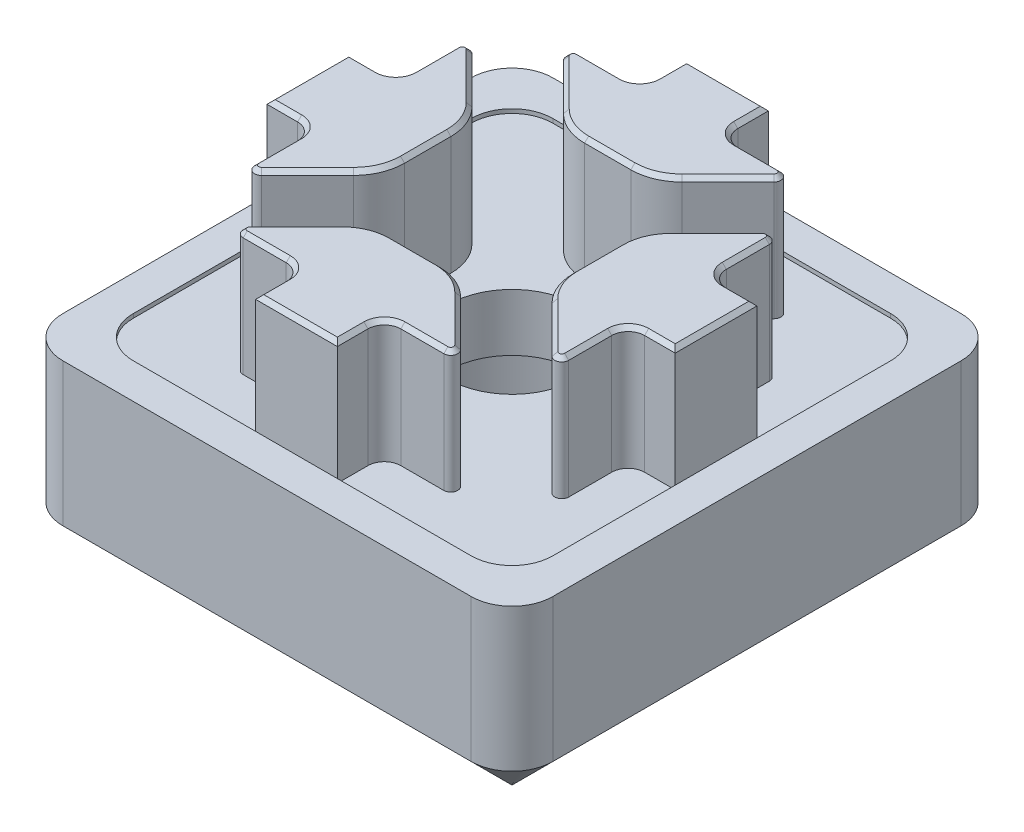
SolidWorks part; units mm, degrees
ref_plane "Front Plane" through (0, 0, 0) normal (0, 0, 1) x (1, 0, 0)
ref_plane "Top Plane" through (0, 0, 0) normal (0, 1, 0) x (1, 0, 0)
ref_plane "Right Plane" through (0, 0, 0) normal (1, 0, 0) x (0, 0, -1)
sketch "Sketch1" plane through (0, 0, 0) normal (0, 1, 0) x (1, 0, 0)
  line L1 (12, 12) -> (-12, 12)
  line L2 (12, 12) -> (12, -12)
  line L3 (12, -12) -> (-12, -12)
  line L4 (-12, 12) -> (-12, -12)
  line L5 (12, 12) -> (-12, -12) construction
  line L6 (12, -12) -> (-12, 12) construction
  circle A0 centre (0, 0) radius 3.15
  point P0 (0, 0)
  dimension "D3" = 6.3
  dimension "D1" = 24
  dimension "D2" = 24
extrude "Boss-Extrude1" add sketch "Sketch1" along normal blind 9
sketch "Sketch2" plane through (0, 9, 0) normal (0, 1, 0) x (1, 0, 0)
  line L1 (10.275, 10.275) -> (-10.275, 10.275)
  line L2 (10.275, 10.275) -> (10.275, -10.275)
  line L3 (10.275, -10.275) -> (-10.275, -10.275)
  line L4 (-10.275, 10.275) -> (-10.275, -10.275)
  line L5 (10.275, 10.275) -> (-10.275, -10.275) construction
  line L6 (10.275, -10.275) -> (-10.275, 10.275) construction
  point P0 (0, 0)
  dimension "D1" = 20.55
extrude "Cut-Extrude1" cut sketch "Sketch2" against normal blind 0.2
sketch "Sketch4" plane through (0, 0, 0) normal (0, -1, 0) x (1, 0, 0)
  circle A0 centre (0, 0) radius 6
extrude "Cut-Extrude2" cut sketch "Sketch4" against normal blind 6
fillet "Fillet1" radius 2 8 edges at (-10.275, 8.9, -10.275) (-10.275, 8.9, 10.275) (10.275, 8.9, 10.275) (10.275, 8.9, -10.275) (12, 4.5, 12) (-12, 4.5, 12) (-12, 4.5, -12) (12, 4.5, -12)
chamfer "Chamfer1" distance 2 angle 45 8 edges at (11.4142, 0, 11.4142) (0, 0, 12) (-11.4142, 0, 11.4142) (-12, 0, 0) (-11.4142, 0, -11.4142) (0, 0, -12) (12, 0, 0) (11.4142, 0, -11.4142)
chamfer "Chamfer2" distance 1 angle 45 1 edges at (0, 0, -6)
sketch "Sketch5" plane through (0, 8.8, 0) normal (0, 1, 0) x (1, 0, 0)
  line L0 (10.275, 9.7148) -> (9.4876, 9.7148)
  line L2 (9.4876, 9.7148) -> (8.7764, 9.7148)
  line L4 (8.7764, 9.7148) -> (8.4716, 9.7148)
  line L6 (8.4716, 9.7148) -> (8.2684, 9.7148)
  line L8 (10.275, 7.7082) -> (10.275, 9.7148)
  line L10 (10.275, 234.725) -> (10.275, 204.7148)
  line L12 (10.275, 204.7148) -> (256.2852, 204.7148)
  line L13 (8.7764, 2.2218) -> (10.275, 2.2218) construction
  line L14 (256.2852, 204.7148) -> (256.2852, 234.725)
  line L16 (256.2852, 234.725) -> (10.275, 234.725)
  line L17 (10.275, -8.275) -> (10.275, 8.275) construction
  line L18 (10.275, 84.7148) -> (256.2852, 84.7148)
  line L20 (256.2852, 84.7148) -> (256.2852, 184.725)
  line L22 (256.2852, 184.725) -> (10.275, 184.725)
  line L24 (10.275, 184.725) -> (10.275, 84.7148)
  line L26 (256.2852, 247.2218) -> (256.2852, 245.8533)
  line L28 (256.2852, 245.8533) -> (256.2852, 243.5865)
  line L30 (256.2852, 243.5865) -> (256.2852, 242.218)
  line L32 (256.2852, 242.218) -> (256.2852, 241.4306)
  line L34 (257.0726, 242.218) -> (257.7838, 242.218)
  line L36 (258.0886, 241.9132) -> (258.0886, 239.805)
  line L38 (259.5195, 239.2123) -> (261.7743, 241.4671)
  line L40 (262.6522, 243.5865) -> (262.6522, 245.8533)
  line L42 (261.7743, 247.9727) -> (259.5195, 250.2275)
  line L44 (258.0886, 249.6348) -> (258.0886, 247.5266)
  line L46 (257.7838, 247.2218) -> (257.0726, 247.2218)
  line L48 (256.2852, 248.0092) -> (256.2852, 247.2218)
  line L50 (256.2852, 234.725) -> (257.0726, 234.725)
  line L52 (257.0726, 234.725) -> (257.7838, 234.725)
  line L54 (257.7838, 234.725) -> (258.0886, 234.725)
  line L56 (258.0886, 234.725) -> (258.2918, 234.725)
  line L58 (256.2852, 236.7316) -> (256.2852, 234.725)
  line L60 (262.9908, 234.725) -> (265.1467, 234.725)
  line L62 (265.1467, 234.725) -> (267.4135, 234.725)
  line L64 (267.4135, 234.725) -> (269.0868, 234.725)
  line L66 (269.0868, 234.725) -> (269.5694, 234.725)
  line L68 (268.782, 235.5124) -> (268.782, 236.2236)
  line L70 (269.0868, 236.5284) -> (271.195, 236.5284)
  line L72 (271.7877, 237.9593) -> (269.5329, 240.2141)
  line L74 (267.4135, 241.092) -> (265.1467, 241.092)
  line L76 (263.0273, 240.2141) -> (260.7725, 237.9593)
  line L78 (261.3652, 236.5284) -> (263.4734, 236.5284)
  line L80 (263.7782, 236.2236) -> (263.7782, 235.5124)
  line L82 (9.4876, 2.2218) -> (8.7764, 2.2218)
  line L84 (8.4716, 2.5266) -> (8.4716, 4.6348)
  line L85 (8.4716, 2.5266) -> (8.4716, 4.6348) construction
  line L86 (7.0407, 5.2275) -> (4.7859, 2.9727)
  line L87 (7.0407, 5.2275) -> (4.7859, 2.9727) construction
  line L88 (3.908, 0.8533) -> (3.908, -1.4135)
  line L89 (3.908, 0.8533) -> (3.908, -1.4135) construction
  line L90 (4.7859, -3.5329) -> (7.0407, -5.7877)
  line L91 (4.7859, -3.5329) -> (7.0407, -5.7877) construction
  line L92 (8.4716, -5.195) -> (8.4716, -3.0868)
  line L93 (8.4716, -5.195) -> (8.4716, -3.0868) construction
  line L94 (8.7764, -2.782) -> (9.4876, -2.782)
  line L96 (10.275, -3.5694) -> (10.275, -3.0868)
  line L98 (10.275, -3.0868) -> (10.275, -2.782)
  line L100 (10.275, -2.782) -> (10.275, -1.4135)
  line L102 (10.275, -1.4135) -> (10.275, 0.8533)
  line L104 (10.275, 0.8533) -> (10.275, 2.5266)
  line L106 (10.275, 2.5266) -> (10.275, 3.0092)
  line L108 (3.0868, 9.7148) -> (2.782, 9.7148)
  line L110 (2.782, 9.7148) -> (1.4135, 9.7148)
  line L112 (1.4135, 9.7148) -> (-0.8533, 9.7148)
  line L114 (-0.8533, 9.7148) -> (-2.5266, 9.7148)
  line L116 (-2.5266, 9.7148) -> (-3.0092, 9.7148)
  line L118 (-2.2218, 8.9274) -> (-2.2218, 8.2162)
  line L120 (-2.5266, 7.9114) -> (-4.6348, 7.9114)
  line L122 (-5.2275, 6.4805) -> (-2.9727, 4.2257)
  line L124 (-0.8533, 3.3478) -> (1.4135, 3.3478)
  line L126 (3.5329, 4.2257) -> (5.7877, 6.4805)
  line L128 (5.195, 7.9114) -> (3.0868, 7.9114)
  line L130 (2.782, 8.2162) -> (2.782, 8.9274)
  line L132 (3.5694, 9.7148) -> (3.0868, 9.7148)
  line L134 (269.0868, 9.7148) -> (268.782, 9.7148)
  line L136 (268.782, 9.7148) -> (267.4135, 9.7148)
  line L138 (267.4135, 9.7148) -> (265.1467, 9.7148)
  line L140 (265.1467, 9.7148) -> (263.4734, 9.7148)
  line L142 (263.4734, 9.7148) -> (262.9908, 9.7148)
  line L144 (263.7782, 8.9274) -> (263.7782, 8.2162)
  line L146 (263.4734, 7.9114) -> (261.3652, 7.9114)
  line L148 (260.7725, 6.4805) -> (263.0273, 4.2257)
  line L150 (265.1467, 3.3478) -> (267.4135, 3.3478)
  line L152 (269.5329, 4.2257) -> (271.7877, 6.4805)
  line L154 (271.195, 7.9114) -> (269.0868, 7.9114)
  line L156 (268.782, 8.2162) -> (268.782, 8.9274)
  line L158 (269.5694, 9.7148) -> (269.0868, 9.7148)
  line L160 (256.2852, 2.5266) -> (256.2852, 2.2218)
  line L162 (256.2852, 2.2218) -> (256.2852, 0.8533)
  line L164 (256.2852, 0.8533) -> (256.2852, -1.4135)
  line L166 (256.2852, -1.4135) -> (256.2852, -3.0868)
  line L168 (256.2852, -3.0868) -> (256.2852, -3.5694)
  line L170 (257.0726, -2.782) -> (257.7838, -2.782)
  line L172 (258.0886, -3.0868) -> (258.0886, -5.195)
  line L174 (259.5195, -5.7877) -> (261.7743, -3.5329)
  line L176 (262.6522, -1.4135) -> (262.6522, 0.8533)
  line L178 (261.7743, 2.9727) -> (259.5195, 5.2275)
  line L180 (258.0886, 4.6348) -> (258.0886, 2.5266)
  line L182 (257.7838, 2.2218) -> (257.0726, 2.2218)
  line L184 (256.2852, 3.0092) -> (256.2852, 2.5266)
  line L186 (-9.7148, 236.7316) -> (-9.7148, 241.4306)
  line L188 (-8.9274, 242.218) -> (-8.2162, 242.218)
  line L190 (-7.9114, 241.9132) -> (-7.9114, 239.805)
  line L192 (-6.4805, 239.2123) -> (-4.2257, 241.4671)
  line L194 (-3.3478, 243.5865) -> (-3.3478, 245.8533)
  line L196 (-4.2257, 247.9727) -> (-6.4805, 250.2275)
  line L198 (-7.9114, 249.6348) -> (-7.9114, 247.5266)
  line L200 (-8.2162, 247.2218) -> (-8.9274, 247.2218)
  line L202 (-9.7148, 248.0092) -> (-9.7148, 252.7082)
  line L204 (-7.7082, 254.7148) -> (-3.0092, 254.7148)
  line L206 (-2.2218, 253.9274) -> (-2.2218, 253.2162)
  line L208 (-2.5266, 252.9114) -> (-4.6348, 252.9114)
  line L210 (-5.2275, 251.4805) -> (-2.9727, 249.2257)
  line L212 (-0.8533, 248.3478) -> (1.4135, 248.3478)
  line L214 (3.5329, 249.2257) -> (5.7877, 251.4805)
  line L216 (5.195, 252.9114) -> (3.0868, 252.9114)
  line L218 (2.782, 253.2162) -> (2.782, 253.9274)
  line L220 (3.5694, 254.7148) -> (8.2684, 254.7148)
  line L222 (10.275, 252.7082) -> (10.275, 252.9114)
  line L224 (10.275, 252.9114) -> (10.275, 253.2162)
  line L226 (10.275, 253.2162) -> (10.275, 253.9274)
  line L228 (10.275, 253.9274) -> (10.275, 254.7148)
  line L230 (10.275, 254.7148) -> (256.2852, 254.7148)
  line L232 (256.2852, 254.7148) -> (256.2852, 252.7082)
  line L234 (258.2918, 254.7148) -> (262.9908, 254.7148)
  line L236 (263.7782, 253.9274) -> (263.7782, 253.2162)
  line L238 (263.4734, 252.9114) -> (261.3652, 252.9114)
  line L240 (260.7725, 251.4805) -> (263.0273, 249.2257)
  line L242 (265.1467, 248.3478) -> (267.4135, 248.3478)
  line L244 (269.5329, 249.2257) -> (271.7877, 251.4805)
  line L246 (271.195, 252.9114) -> (269.0868, 252.9114)
  line L248 (268.782, 253.2162) -> (268.782, 253.9274)
  line L250 (269.5694, 254.7148) -> (274.2684, 254.7148)
  line L252 (276.275, 252.7082) -> (276.275, 248.0092)
  line L254 (275.4876, 247.2218) -> (274.7764, 247.2218)
  line L256 (274.4716, 247.5266) -> (274.4716, 249.6348)
  line L258 (273.0407, 250.2275) -> (270.7859, 247.9727)
  line L260 (269.908, 245.8533) -> (269.908, 243.5865)
  line L262 (270.7859, 241.4671) -> (273.0407, 239.2123)
  line L264 (274.4716, 239.805) -> (274.4716, 241.9132)
  line L266 (274.7764, 242.218) -> (275.4876, 242.218)
  line L268 (276.275, 241.4306) -> (276.275, 236.7316)
  line L270 (274.2684, 234.725) -> (274.4716, 234.725)
  line L272 (274.4716, 234.725) -> (274.7764, 234.725)
  line L274 (274.7764, 234.725) -> (275.4876, 234.725)
  line L276 (275.4876, 234.725) -> (276.275, 234.725)
  line L278 (276.275, 234.725) -> (276.275, 9.7148)
  line L280 (276.275, 9.7148) -> (275.4876, 9.7148)
  line L282 (275.4876, 9.7148) -> (274.7764, 9.7148)
  line L284 (274.7764, 9.7148) -> (274.4716, 9.7148)
  line L286 (274.4716, 9.7148) -> (274.2684, 9.7148)
  line L288 (276.275, 7.7082) -> (276.275, 3.0092)
  line L290 (275.4876, 2.2218) -> (274.7764, 2.2218)
  line L292 (274.4716, 2.5266) -> (274.4716, 4.6348)
  line L294 (273.0407, 5.2275) -> (270.7859, 2.9727)
  line L296 (269.908, 0.8533) -> (269.908, -1.4135)
  line L298 (270.7859, -3.5329) -> (273.0407, -5.7877)
  line L300 (274.4716, -5.195) -> (274.4716, -3.0868)
  line L302 (274.7764, -2.782) -> (275.4876, -2.782)
  line L304 (276.275, -3.5694) -> (276.275, -8.2684)
  line L306 (274.2684, -10.275) -> (269.5694, -10.275)
  line L308 (268.782, -9.4876) -> (268.782, -8.7764)
  line L310 (269.0868, -8.4716) -> (271.195, -8.4716)
  line L312 (271.7877, -7.0407) -> (269.5329, -4.7859)
  line L314 (267.4135, -3.908) -> (265.1467, -3.908)
  line L316 (263.0273, -4.7859) -> (260.7725, -7.0407)
  line L318 (261.3652, -8.4716) -> (263.4734, -8.4716)
  line L320 (263.7782, -8.7764) -> (263.7782, -9.4876)
  line L322 (262.9908, -10.275) -> (258.2918, -10.275)
  line L324 (256.2852, -8.2684) -> (256.2852, -8.4716)
  line L326 (256.2852, -8.4716) -> (256.2852, -8.7764)
  line L328 (256.2852, -8.7764) -> (256.2852, -9.4876)
  line L330 (256.2852, -9.4876) -> (256.2852, -10.275)
  line L332 (256.2852, -10.275) -> (10.275, -10.275)
  line L334 (10.275, -10.275) -> (10.275, -9.4876)
  line L336 (10.275, -9.4876) -> (10.275, -8.7764)
  line L338 (10.275, -8.7764) -> (10.275, -8.4716)
  line L340 (10.275, -8.4716) -> (10.275, -8.2684)
  line L341 (10.275, -8.4716) -> (10.275, -8.2684)
  line L342 (8.2684, -10.275) -> (3.5694, -10.275)
  line L344 (2.782, -9.4876) -> (2.782, -8.7764)
  line L346 (3.0868, -8.4716) -> (5.195, -8.4716)
  line L348 (5.7877, -7.0407) -> (3.5329, -4.7859)
  line L350 (1.4135, -3.908) -> (-0.8533, -3.908)
  line L352 (-2.9727, -4.7859) -> (-5.2275, -7.0407)
  line L354 (-4.6348, -8.4716) -> (-2.5266, -8.4716)
  line L356 (-2.2218, -8.7764) -> (-2.2218, -9.4876)
  line L358 (-3.0092, -10.275) -> (-7.7082, -10.275)
  line L360 (-9.7148, -8.2684) -> (-9.7148, -3.5694)
  line L362 (-8.9274, -2.782) -> (-8.2162, -2.782)
  line L364 (-7.9114, -3.0868) -> (-7.9114, -5.195)
  line L366 (-6.4805, -5.7877) -> (-4.2257, -3.5329)
  line L368 (-3.3478, -1.4135) -> (-3.3478, 0.8533)
  line L370 (-4.2257, 2.9727) -> (-6.4805, 5.2275)
  line L372 (-7.9114, 4.6348) -> (-7.9114, 2.5266)
  line L374 (-8.2162, 2.2218) -> (-8.9274, 2.2218)
  line L376 (-9.7148, 3.0092) -> (-9.7148, 7.7082)
  line L378 (-7.7082, 9.7148) -> (-7.9114, 9.7148)
  line L380 (-7.9114, 9.7148) -> (-8.2162, 9.7148)
  line L382 (-8.2162, 9.7148) -> (-8.9274, 9.7148)
  line L384 (-8.9274, 9.7148) -> (-9.7148, 9.7148)
  line L386 (-9.7148, 9.7148) -> (-9.7148, 234.725)
  line L388 (-9.7148, 234.725) -> (-8.9274, 234.725)
  line L390 (-8.9274, 234.725) -> (-8.2162, 234.725)
  line L392 (-8.2162, 234.725) -> (-7.9114, 234.725)
  line L394 (-7.9114, 234.725) -> (-7.7082, 234.725)
  line L396 (-2.5266, 234.725) -> (-2.2218, 234.725)
  line L398 (-2.2218, 234.725) -> (-0.8533, 234.725)
  line L400 (-0.8533, 234.725) -> (1.4135, 234.725)
  line L402 (1.4135, 234.725) -> (3.0868, 234.725)
  line L404 (3.0868, 234.725) -> (3.5694, 234.725)
  line L406 (2.782, 235.5124) -> (2.782, 236.2236)
  line L408 (3.0868, 236.5284) -> (5.195, 236.5284)
  line L410 (5.7877, 237.9593) -> (3.5329, 240.2141)
  line L412 (1.4135, 241.092) -> (-0.8533, 241.092)
  line L414 (-2.9727, 240.2141) -> (-5.2275, 237.9593)
  line L416 (-4.6348, 236.5284) -> (-2.5266, 236.5284)
  line L418 (-2.2218, 236.2236) -> (-2.2218, 235.5124)
  line L420 (-3.0092, 234.725) -> (-2.5266, 234.725)
  line L422 (8.4716, 234.725) -> (8.7764, 234.725)
  line L424 (8.7764, 234.725) -> (9.4876, 234.725)
  line L426 (9.4876, 234.725) -> (10.275, 234.725)
  line L428 (10.275, 234.725) -> (10.275, 236.7316)
  line L430 (8.2684, 234.725) -> (8.4716, 234.725)
  line L432 (9.4876, 247.2218) -> (8.7764, 247.2218)
  line L434 (8.4716, 247.5266) -> (8.4716, 249.6348)
  line L436 (7.0407, 250.2275) -> (4.7859, 247.9727)
  line L438 (3.908, 245.8533) -> (3.908, 243.5865)
  line L440 (4.7859, 241.4671) -> (7.0407, 239.2123)
  line L442 (8.4716, 239.805) -> (8.4716, 241.9132)
  line L444 (8.7764, 242.218) -> (9.4876, 242.218)
  line L446 (10.275, 241.4306) -> (10.275, 242.218)
  line L448 (10.275, 242.218) -> (10.275, 243.5865)
  line L450 (10.275, 243.5865) -> (10.275, 245.8533)
  line L452 (10.275, 245.8533) -> (10.275, 248.0092)
  line L454 (256.2852, 8.9274) -> (256.2852, 8.2162)
  line L456 (256.2852, 8.2162) -> (256.2852, 7.9114)
  line L458 (256.2852, 7.9114) -> (256.2852, 7.7082)
  line L460 (258.2918, 9.7148) -> (256.2852, 9.7148)
  line L462 (256.2852, 9.7148) -> (256.2852, 8.9274)
  line L464 (256.2852, 9.7148) -> (256.2852, 64.725)
  line L466 (256.2852, 64.725) -> (10.275, 64.725)
  line L467 (8.7764, -2.782) -> (10.275, -2.782) construction
  line L468 (10.275, 64.725) -> (10.275, 9.7148)
  line L470 (10.275, 9.7148) -> (256.2852, 9.7148)
  line L471 (10.275, 2.2218) -> (10.275, -2.782) construction
  line L475 (7.9716, -5.195) -> (7.9716, -3.0868)
  line L476 (5.1394, -3.1793) -> (7.3943, -5.4341)
  line L477 (4.408, 0.8533) -> (4.408, -1.4135)
  line L478 (7.3943, 4.8739) -> (5.1394, 2.6191)
  line L479 (7.9716, 2.5266) -> (7.9716, 4.6348)
  line L480 (8.7764, -2.282) -> (10.275, -2.282)
  line L481 (8.7764, 1.7218) -> (10.275, 1.7218)
  line L482 (10.275, 1.7218) -> (10.275, -2.282)
  line L483 (1.7218, -10.275) -> (-2.282, -10.275)
  line L484 (-2.282, -8.7764) -> (-2.282, -10.275)
  line L485 (-5.195, -7.9716) -> (-3.0868, -7.9716)
  line L486 (-3.1793, -5.1394) -> (-5.4341, -7.3943)
  line L487 (0.8533, -4.408) -> (-1.4135, -4.408)
  line L488 (4.8739, -7.3943) -> (2.6191, -5.1394)
  line L489 (2.5266, -7.9716) -> (4.6348, -7.9716)
  line L490 (1.7218, -8.7764) -> (1.7218, -10.275)
  line L491 (-10.275, -1.7218) -> (-10.275, 2.282)
  line L492 (-8.7764, 2.282) -> (-10.275, 2.282)
  line L493 (-7.9716, 5.195) -> (-7.9716, 3.0868)
  line L494 (-5.1394, 3.1793) -> (-7.3943, 5.4341)
  line L495 (-4.408, -0.8533) -> (-4.408, 1.4135)
  line L496 (-7.3943, -4.8739) -> (-5.1394, -2.6191)
  line L497 (-7.9716, -2.5266) -> (-7.9716, -4.6348)
  line L498 (-8.7764, -1.7218) -> (-10.275, -1.7218)
  line L499 (-1.7218, 10.275) -> (2.282, 10.275)
  line L500 (2.282, 8.7764) -> (2.282, 10.275)
  line L501 (5.195, 7.9716) -> (3.0868, 7.9716)
  line L502 (3.1793, 5.1394) -> (5.4341, 7.3943)
  line L503 (-0.8533, 4.408) -> (1.4135, 4.408)
  line L504 (-4.8739, 7.3943) -> (-2.6191, 5.1394)
  line L505 (-2.5266, 7.9716) -> (-4.6348, 7.9716)
  line L506 (-1.7218, 8.7764) -> (-1.7218, 10.275)
  line L716 (9.775, 1.7218) -> (9.775, -2.282) construction
  line L717 (8.7764, -2.282) -> (9.775, -2.282) construction
  line L718 (8.7764, 1.7218) -> (9.775, 1.7218) construction
  arc A0 (10.275, 7.7082) -> (8.2684, 9.7148) centre (8.2684, 7.7082) ccw
  circle A2 centre (266.2801, 244.7199) radius 2.1463
  arc A4 (257.0726, 242.218) -> (256.2852, 241.4306) centre (257.0726, 241.4306) ccw
  arc A6 (258.0886, 241.9132) -> (257.7838, 242.218) centre (257.7838, 241.9132) ccw
  arc A8 (258.0886, 239.805) -> (259.5195, 239.2123) centre (258.9268, 239.805) ccw
  arc A10 (261.7743, 241.4671) -> (262.6522, 243.5865) centre (259.655, 243.5865) ccw
  arc A12 (262.6522, 245.8533) -> (261.7743, 247.9727) centre (259.655, 245.8533) ccw
  arc A14 (259.5195, 250.2275) -> (258.0886, 249.6348) centre (258.9268, 249.6348) ccw
  arc A16 (257.7838, 247.2218) -> (258.0886, 247.5266) centre (257.7838, 247.5266) ccw
  arc A18 (256.2852, 248.0092) -> (257.0726, 247.2218) centre (257.0726, 248.0092) ccw
  arc A20 (256.2852, 236.7316) -> (258.2918, 234.725) centre (258.2918, 236.7316) ccw
  arc A22 (268.782, 235.5124) -> (269.5694, 234.725) centre (269.5694, 235.5124) ccw
  arc A24 (269.0868, 236.5284) -> (268.782, 236.2236) centre (269.0868, 236.2236) ccw
  arc A26 (271.195, 236.5284) -> (271.7877, 237.9593) centre (271.195, 237.3666) ccw
  arc A28 (269.5329, 240.2141) -> (267.4135, 241.092) centre (267.4135, 238.0948) ccw
  arc A30 (265.1467, 241.092) -> (263.0273, 240.2141) centre (265.1467, 238.0948) ccw
  arc A32 (260.7725, 237.9593) -> (261.3652, 236.5284) centre (261.3652, 237.3666) ccw
  arc A34 (263.7782, 236.2236) -> (263.4734, 236.5284) centre (263.4734, 236.2236) ccw
  arc A36 (262.9908, 234.725) -> (263.7782, 235.5124) centre (262.9908, 235.5124) ccw
  circle A38 centre (0.2801, -0.2801) radius 2.1463
  arc A40 (8.4716, 2.5266) -> (8.7764, 2.2218) centre (8.7764, 2.5266) ccw
  arc A41 (8.4716, 2.5266) -> (8.7764, 2.2218) centre (8.7764, 2.5266) ccw construction
  arc A42 (8.4716, 4.6348) -> (7.0407, 5.2275) centre (7.6334, 4.6348) ccw
  arc A43 (8.4716, 4.6348) -> (7.0407, 5.2275) centre (7.6334, 4.6348) ccw construction
  arc A44 (4.7859, 2.9727) -> (3.908, 0.8533) centre (6.9052, 0.8533) ccw
  arc A45 (4.7859, 2.9727) -> (3.908, 0.8533) centre (6.9052, 0.8533) ccw construction
  arc A46 (3.908, -1.4135) -> (4.7859, -3.5329) centre (6.9052, -1.4135) ccw
  arc A47 (3.908, -1.4135) -> (4.7859, -3.5329) centre (6.9052, -1.4135) ccw construction
  arc A48 (7.0407, -5.7877) -> (8.4716, -5.195) centre (7.6334, -5.195) ccw
  arc A49 (7.0407, -5.7877) -> (8.4716, -5.195) centre (7.6334, -5.195) ccw construction
  arc A50 (8.7764, -2.782) -> (8.4716, -3.0868) centre (8.7764, -3.0868) ccw
  arc A51 (8.7764, -2.782) -> (8.4716, -3.0868) centre (8.7764, -3.0868) ccw construction
  arc A52 (10.275, -3.5694) -> (9.4876, -2.782) centre (9.4876, -3.5694) ccw
  arc A54 (9.4876, 2.2218) -> (10.275, 3.0092) centre (9.4876, 3.0092) ccw
  arc A56 (-2.2218, 8.9274) -> (-3.0092, 9.7148) centre (-3.0092, 8.9274) ccw
  arc A58 (-2.5266, 7.9114) -> (-2.2218, 8.2162) centre (-2.5266, 8.2162) ccw
  arc A60 (-4.6348, 7.9114) -> (-5.2275, 6.4805) centre (-4.6348, 7.0732) ccw
  arc A62 (-2.9727, 4.2257) -> (-0.8533, 3.3478) centre (-0.8533, 6.345) ccw
  arc A64 (1.4135, 3.3478) -> (3.5329, 4.2257) centre (1.4135, 6.345) ccw
  arc A66 (5.7877, 6.4805) -> (5.195, 7.9114) centre (5.195, 7.0732) ccw
  arc A68 (2.782, 8.2162) -> (3.0868, 7.9114) centre (3.0868, 8.2162) ccw
  arc A70 (3.5694, 9.7148) -> (2.782, 8.9274) centre (3.5694, 8.9274) ccw
  circle A72 centre (266.2801, -0.2801) radius 2.1463
  arc A74 (263.7782, 8.9274) -> (262.9908, 9.7148) centre (262.9908, 8.9274) ccw
  arc A76 (263.4734, 7.9114) -> (263.7782, 8.2162) centre (263.4734, 8.2162) ccw
  arc A78 (261.3652, 7.9114) -> (260.7725, 6.4805) centre (261.3652, 7.0732) ccw
  arc A80 (263.0273, 4.2257) -> (265.1467, 3.3478) centre (265.1467, 6.345) ccw
  arc A82 (267.4135, 3.3478) -> (269.5329, 4.2257) centre (267.4135, 6.345) ccw
  arc A84 (271.7877, 6.4805) -> (271.195, 7.9114) centre (271.195, 7.0732) ccw
  arc A86 (268.782, 8.2162) -> (269.0868, 7.9114) centre (269.0868, 8.2162) ccw
  arc A88 (269.5694, 9.7148) -> (268.782, 8.9274) centre (269.5694, 8.9274) ccw
  arc A90 (257.0726, -2.782) -> (256.2852, -3.5694) centre (257.0726, -3.5694) ccw
  arc A92 (258.0886, -3.0868) -> (257.7838, -2.782) centre (257.7838, -3.0868) ccw
  arc A94 (258.0886, -5.195) -> (259.5195, -5.7877) centre (258.9268, -5.195) ccw
  arc A96 (261.7743, -3.5329) -> (262.6522, -1.4135) centre (259.655, -1.4135) ccw
  arc A98 (262.6522, 0.8533) -> (261.7743, 2.9727) centre (259.655, 0.8533) ccw
  arc A100 (259.5195, 5.2275) -> (258.0886, 4.6348) centre (258.9268, 4.6348) ccw
  arc A102 (257.7838, 2.2218) -> (258.0886, 2.5266) centre (257.7838, 2.5266) ccw
  arc A104 (256.2852, 3.0092) -> (257.0726, 2.2218) centre (257.0726, 3.0092) ccw
  circle A106 centre (0.2801, 244.7199) radius 2.1463
  arc A108 (-8.9274, 242.218) -> (-9.7148, 241.4306) centre (-8.9274, 241.4306) ccw
  arc A110 (-7.9114, 241.9132) -> (-8.2162, 242.218) centre (-8.2162, 241.9132) ccw
  arc A112 (-7.9114, 239.805) -> (-6.4805, 239.2123) centre (-7.0732, 239.805) ccw
  arc A114 (-4.2257, 241.4671) -> (-3.3478, 243.5865) centre (-6.345, 243.5865) ccw
  arc A116 (-3.3478, 245.8533) -> (-4.2257, 247.9727) centre (-6.345, 245.8533) ccw
  arc A118 (-6.4805, 250.2275) -> (-7.9114, 249.6348) centre (-7.0732, 249.6348) ccw
  arc A120 (-8.2162, 247.2218) -> (-7.9114, 247.5266) centre (-8.2162, 247.5266) ccw
  arc A122 (-9.7148, 248.0092) -> (-8.9274, 247.2218) centre (-8.9274, 248.0092) ccw
  arc A124 (-7.7082, 254.7148) -> (-9.7148, 252.7082) centre (-7.7082, 252.7082) ccw
  arc A126 (-2.2218, 253.9274) -> (-3.0092, 254.7148) centre (-3.0092, 253.9274) ccw
  arc A128 (-2.5266, 252.9114) -> (-2.2218, 253.2162) centre (-2.5266, 253.2162) ccw
  arc A130 (-4.6348, 252.9114) -> (-5.2275, 251.4805) centre (-4.6348, 252.0732) ccw
  arc A132 (-2.9727, 249.2257) -> (-0.8533, 248.3478) centre (-0.8533, 251.345) ccw
  arc A134 (1.4135, 248.3478) -> (3.5329, 249.2257) centre (1.4135, 251.345) ccw
  arc A136 (5.7877, 251.4805) -> (5.195, 252.9114) centre (5.195, 252.0732) ccw
  arc A138 (2.782, 253.2162) -> (3.0868, 252.9114) centre (3.0868, 253.2162) ccw
  arc A140 (3.5694, 254.7148) -> (2.782, 253.9274) centre (3.5694, 253.9274) ccw
  arc A142 (10.275, 252.7082) -> (8.2684, 254.7148) centre (8.2684, 252.7082) ccw
  arc A144 (258.2918, 254.7148) -> (256.2852, 252.7082) centre (258.2918, 252.7082) ccw
  arc A146 (263.7782, 253.9274) -> (262.9908, 254.7148) centre (262.9908, 253.9274) ccw
  arc A148 (263.4734, 252.9114) -> (263.7782, 253.2162) centre (263.4734, 253.2162) ccw
  arc A150 (261.3652, 252.9114) -> (260.7725, 251.4805) centre (261.3652, 252.0732) ccw
  arc A152 (263.0273, 249.2257) -> (265.1467, 248.3478) centre (265.1467, 251.345) ccw
  arc A154 (267.4135, 248.3478) -> (269.5329, 249.2257) centre (267.4135, 251.345) ccw
  arc A156 (271.7877, 251.4805) -> (271.195, 252.9114) centre (271.195, 252.0732) ccw
  arc A158 (268.782, 253.2162) -> (269.0868, 252.9114) centre (269.0868, 253.2162) ccw
  arc A160 (269.5694, 254.7148) -> (268.782, 253.9274) centre (269.5694, 253.9274) ccw
  arc A162 (276.275, 252.7082) -> (274.2684, 254.7148) centre (274.2684, 252.7082) ccw
  arc A164 (275.4876, 247.2218) -> (276.275, 248.0092) centre (275.4876, 248.0092) ccw
  arc A166 (274.4716, 247.5266) -> (274.7764, 247.2218) centre (274.7764, 247.5266) ccw
  arc A168 (274.4716, 249.6348) -> (273.0407, 250.2275) centre (273.6334, 249.6348) ccw
  arc A170 (270.7859, 247.9727) -> (269.908, 245.8533) centre (272.9052, 245.8533) ccw
  arc A172 (269.908, 243.5865) -> (270.7859, 241.4671) centre (272.9052, 243.5865) ccw
  arc A174 (273.0407, 239.2123) -> (274.4716, 239.805) centre (273.6334, 239.805) ccw
  arc A176 (274.7764, 242.218) -> (274.4716, 241.9132) centre (274.7764, 241.9132) ccw
  arc A178 (276.275, 241.4306) -> (275.4876, 242.218) centre (275.4876, 241.4306) ccw
  arc A180 (274.2684, 234.725) -> (276.275, 236.7316) centre (274.2684, 236.7316) ccw
  arc A182 (276.275, 7.7082) -> (274.2684, 9.7148) centre (274.2684, 7.7082) ccw
  arc A184 (275.4876, 2.2218) -> (276.275, 3.0092) centre (275.4876, 3.0092) ccw
  arc A186 (274.4716, 2.5266) -> (274.7764, 2.2218) centre (274.7764, 2.5266) ccw
  arc A188 (274.4716, 4.6348) -> (273.0407, 5.2275) centre (273.6334, 4.6348) ccw
  arc A190 (270.7859, 2.9727) -> (269.908, 0.8533) centre (272.9052, 0.8533) ccw
  arc A192 (269.908, -1.4135) -> (270.7859, -3.5329) centre (272.9052, -1.4135) ccw
  arc A194 (273.0407, -5.7877) -> (274.4716, -5.195) centre (273.6334, -5.195) ccw
  arc A196 (274.7764, -2.782) -> (274.4716, -3.0868) centre (274.7764, -3.0868) ccw
  arc A198 (276.275, -3.5694) -> (275.4876, -2.782) centre (275.4876, -3.5694) ccw
  arc A200 (274.2684, -10.275) -> (276.275, -8.2684) centre (274.2684, -8.2684) ccw
  arc A202 (268.782, -9.4876) -> (269.5694, -10.275) centre (269.5694, -9.4876) ccw
  arc A204 (269.0868, -8.4716) -> (268.782, -8.7764) centre (269.0868, -8.7764) ccw
  arc A206 (271.195, -8.4716) -> (271.7877, -7.0407) centre (271.195, -7.6334) ccw
  arc A208 (269.5329, -4.7859) -> (267.4135, -3.908) centre (267.4135, -6.9052) ccw
  arc A210 (265.1467, -3.908) -> (263.0273, -4.7859) centre (265.1467, -6.9052) ccw
  arc A212 (260.7725, -7.0407) -> (261.3652, -8.4716) centre (261.3652, -7.6334) ccw
  arc A214 (263.7782, -8.7764) -> (263.4734, -8.4716) centre (263.4734, -8.7764) ccw
  arc A216 (262.9908, -10.275) -> (263.7782, -9.4876) centre (262.9908, -9.4876) ccw
  arc A218 (256.2852, -8.2684) -> (258.2918, -10.275) centre (258.2918, -8.2684) ccw
  arc A220 (8.2684, -10.275) -> (10.275, -8.2684) centre (8.2684, -8.2684) ccw
  arc A222 (2.782, -9.4876) -> (3.5694, -10.275) centre (3.5694, -9.4876) ccw
  arc A224 (3.0868, -8.4716) -> (2.782, -8.7764) centre (3.0868, -8.7764) ccw
  arc A226 (5.195, -8.4716) -> (5.7877, -7.0407) centre (5.195, -7.6334) ccw
  arc A228 (3.5329, -4.7859) -> (1.4135, -3.908) centre (1.4135, -6.9052) ccw
  arc A230 (-0.8533, -3.908) -> (-2.9727, -4.7859) centre (-0.8533, -6.9052) ccw
  arc A232 (-5.2275, -7.0407) -> (-4.6348, -8.4716) centre (-4.6348, -7.6334) ccw
  arc A234 (-2.2218, -8.7764) -> (-2.5266, -8.4716) centre (-2.5266, -8.7764) ccw
  arc A236 (-3.0092, -10.275) -> (-2.2218, -9.4876) centre (-3.0092, -9.4876) ccw
  arc A238 (-9.7148, -8.2684) -> (-7.7082, -10.275) centre (-7.7082, -8.2684) ccw
  arc A240 (-8.9274, -2.782) -> (-9.7148, -3.5694) centre (-8.9274, -3.5694) ccw
  arc A242 (-7.9114, -3.0868) -> (-8.2162, -2.782) centre (-8.2162, -3.0868) ccw
  arc A244 (-7.9114, -5.195) -> (-6.4805, -5.7877) centre (-7.0732, -5.195) ccw
  arc A246 (-4.2257, -3.5329) -> (-3.3478, -1.4135) centre (-6.345, -1.4135) ccw
  arc A248 (-3.3478, 0.8533) -> (-4.2257, 2.9727) centre (-6.345, 0.8533) ccw
  arc A250 (-6.4805, 5.2275) -> (-7.9114, 4.6348) centre (-7.0732, 4.6348) ccw
  arc A252 (-8.2162, 2.2218) -> (-7.9114, 2.5266) centre (-8.2162, 2.5266) ccw
  arc A254 (-9.7148, 3.0092) -> (-8.9274, 2.2218) centre (-8.9274, 3.0092) ccw
  arc A256 (-7.7082, 9.7148) -> (-9.7148, 7.7082) centre (-7.7082, 7.7082) ccw
  arc A258 (-9.7148, 236.7316) -> (-7.7082, 234.725) centre (-7.7082, 236.7316) ccw
  arc A260 (2.782, 235.5124) -> (3.5694, 234.725) centre (3.5694, 235.5124) ccw
  arc A262 (3.0868, 236.5284) -> (2.782, 236.2236) centre (3.0868, 236.2236) ccw
  arc A264 (5.195, 236.5284) -> (5.7877, 237.9593) centre (5.195, 237.3666) ccw
  arc A266 (3.5329, 240.2141) -> (1.4135, 241.092) centre (1.4135, 238.0948) ccw
  arc A268 (-0.8533, 241.092) -> (-2.9727, 240.2141) centre (-0.8533, 238.0948) ccw
  arc A270 (-5.2275, 237.9593) -> (-4.6348, 236.5284) centre (-4.6348, 237.3666) ccw
  arc A272 (-2.2218, 236.2236) -> (-2.5266, 236.5284) centre (-2.5266, 236.2236) ccw
  arc A274 (-3.0092, 234.725) -> (-2.2218, 235.5124) centre (-3.0092, 235.5124) ccw
  arc A276 (8.2684, 234.725) -> (10.275, 236.7316) centre (8.2684, 236.7316) ccw
  arc A278 (9.4876, 247.2218) -> (10.275, 248.0092) centre (9.4876, 248.0092) ccw
  arc A280 (8.4716, 247.5266) -> (8.7764, 247.2218) centre (8.7764, 247.5266) ccw
  arc A282 (8.4716, 249.6348) -> (7.0407, 250.2275) centre (7.6334, 249.6348) ccw
  arc A284 (4.7859, 247.9727) -> (3.908, 245.8533) centre (6.9052, 245.8533) ccw
  arc A286 (3.908, 243.5865) -> (4.7859, 241.4671) centre (6.9052, 243.5865) ccw
  arc A288 (7.0407, 239.2123) -> (8.4716, 239.805) centre (7.6334, 239.805) ccw
  arc A290 (8.7764, 242.218) -> (8.4716, 241.9132) centre (8.7764, 241.9132) ccw
  arc A292 (10.275, 241.4306) -> (9.4876, 242.218) centre (9.4876, 241.4306) ccw
  arc A294 (258.2918, 9.7148) -> (256.2852, 7.7082) centre (258.2918, 7.7082) ccw
  arc A296 (8.7764, -2.282) -> (7.9716, -3.0868) centre (8.7764, -3.0868) ccw
  arc A297 (7.3943, -5.4341) -> (7.9716, -5.195) centre (7.6334, -5.195) ccw
  arc A298 (4.408, -1.4135) -> (5.1394, -3.1793) centre (6.9052, -1.4135) ccw
  arc A299 (5.1394, 2.6191) -> (4.408, 0.8533) centre (6.9052, 0.8533) ccw
  arc A300 (7.9716, 4.6348) -> (7.3943, 4.8739) centre (7.6334, 4.6348) ccw
  arc A301 (7.9716, 2.5266) -> (8.7764, 1.7218) centre (8.7764, 2.5266) ccw
  arc A302 (-2.282, -8.7764) -> (-3.0868, -7.9716) centre (-3.0868, -8.7764) ccw
  arc A303 (-5.4341, -7.3943) -> (-5.195, -7.9716) centre (-5.195, -7.6334) ccw
  arc A304 (-1.4135, -4.408) -> (-3.1793, -5.1394) centre (-1.4135, -6.9052) ccw
  arc A305 (2.6191, -5.1394) -> (0.8533, -4.408) centre (0.8533, -6.9052) ccw
  arc A306 (4.6348, -7.9716) -> (4.8739, -7.3943) centre (4.6348, -7.6334) ccw
  arc A307 (2.5266, -7.9716) -> (1.7218, -8.7764) centre (2.5266, -8.7764) ccw
  arc A308 (-8.7764, 2.282) -> (-7.9716, 3.0868) centre (-8.7764, 3.0868) ccw
  arc A309 (-7.3943, 5.4341) -> (-7.9716, 5.195) centre (-7.6334, 5.195) ccw
  arc A310 (-4.408, 1.4135) -> (-5.1394, 3.1793) centre (-6.9052, 1.4135) ccw
  arc A311 (-5.1394, -2.6191) -> (-4.408, -0.8533) centre (-6.9052, -0.8533) ccw
  arc A312 (-7.9716, -4.6348) -> (-7.3943, -4.8739) centre (-7.6334, -4.6348) ccw
  arc A313 (-7.9716, -2.5266) -> (-8.7764, -1.7218) centre (-8.7764, -2.5266) ccw
  arc A314 (2.282, 8.7764) -> (3.0868, 7.9716) centre (3.0868, 8.7764) ccw
  arc A315 (5.4341, 7.3943) -> (5.195, 7.9716) centre (5.195, 7.6334) ccw
  arc A316 (1.4135, 4.408) -> (3.1793, 5.1394) centre (1.4135, 6.9052) ccw
  arc A317 (-2.6191, 5.1394) -> (-0.8533, 4.408) centre (-0.8533, 6.9052) ccw
  arc A318 (-4.6348, 7.9716) -> (-4.8739, 7.3943) centre (-4.6348, 7.6334) ccw
  arc A319 (-2.5266, 7.9716) -> (-1.7218, 8.7764) centre (-2.5266, 8.7764) ccw
  point P617 (0, 0)
  line M212 (8.275, 10.275) -> (-8.275, 10.275)
  line M214 (-10.275, 8.275) -> (-10.275, -8.275)
  line M216 (-8.275, -10.275) -> (8.275, -10.275)
  line M218 (10.275, -8.275) -> (10.275, 8.275)
  dimension "D1" = 0.5
  dimension "D2" = 4
extrude "Boss-Extrude2" add sketch "Sketch5" along normal blind 6 contours A319 L505 A318 L504 A317 L503 A316 L502 A315 L501 A314 L500 L506 M212 | A313 L497 A312 L496 A311 L495 A310 L494 A309 L493 A308 L492 L498 M214 | A307 L489 A306 L488 A305 L487 A304 L486 A303 L485 A302 L484 L490 M216 | A301 L479 A300 L478 A299 L477 A298 L476 A297 L475 A296 L480 L481 M218
chamfer "Chamfer3" distance 0.2 angle 45 56 edges at (-1.7218, 14.8, -9.5257) (0.2801, 14.8, -10.275) (2.282, 14.8, -9.5257) (2.5177, 14.8, -8.2073) (4.1409, 14.8, -7.9716) (5.5075, 14.8, -7.7628) (4.3067, 14.8, -6.2668) (2.3692, 14.8, -4.5981) (0.2801, 14.8, -4.408) (-1.809, 14.8, -4.5981) (-3.7465, 14.8, -6.2668) (-4.9473, 14.8, -7.7628) (-3.5807, 14.8, -7.9716) (-1.9575, 14.8, -8.2073) (-9.5257, 14.8, 1.7218) (-10.275, 14.8, -0.2801) (-9.5257, 14.8, -2.282) (-8.2073, 14.8, -2.5177) (-7.9716, 14.8, -4.1409) (-7.7628, 14.8, -5.5075) (-6.2668, 14.8, -4.3067) (-4.5981, 14.8, -2.3692) (-4.408, 14.8, -0.2801) (-4.5981, 14.8, 1.809) (-6.2668, 14.8, 3.7465) (-7.7628, 14.8, 4.9473) (-7.9716, 14.8, 3.5807) (-8.2073, 14.8, 1.9575) (1.7218, 14.8, 9.5257) (-0.2801, 14.8, 10.275) (-2.282, 14.8, 9.5257) (-2.5177, 14.8, 8.2073) (-4.1409, 14.8, 7.9716) (-5.5075, 14.8, 7.7628) (-4.3067, 14.8, 6.2668) (-2.3692, 14.8, 4.5981) (-0.2801, 14.8, 4.408) (1.809, 14.8, 4.5981) (3.7465, 14.8, 6.2668) (4.9473, 14.8, 7.7628) (3.5807, 14.8, 7.9716) (1.9575, 14.8, 8.2073) (9.5257, 14.8, -1.7218) (10.275, 14.8, 0.2801) (9.5257, 14.8, 2.282) (8.2073, 14.8, 2.5177) (7.9716, 14.8, 4.1409) (7.7628, 14.8, 5.5075) (6.2668, 14.8, 4.3067) (4.5981, 14.8, 2.3692) (4.408, 14.8, 0.2801) (4.5981, 14.8, -1.809) (6.2668, 14.8, -3.7465) (7.7628, 14.8, -4.9473) (7.9716, 14.8, -3.5807) (8.2073, 14.8, -1.9575)
